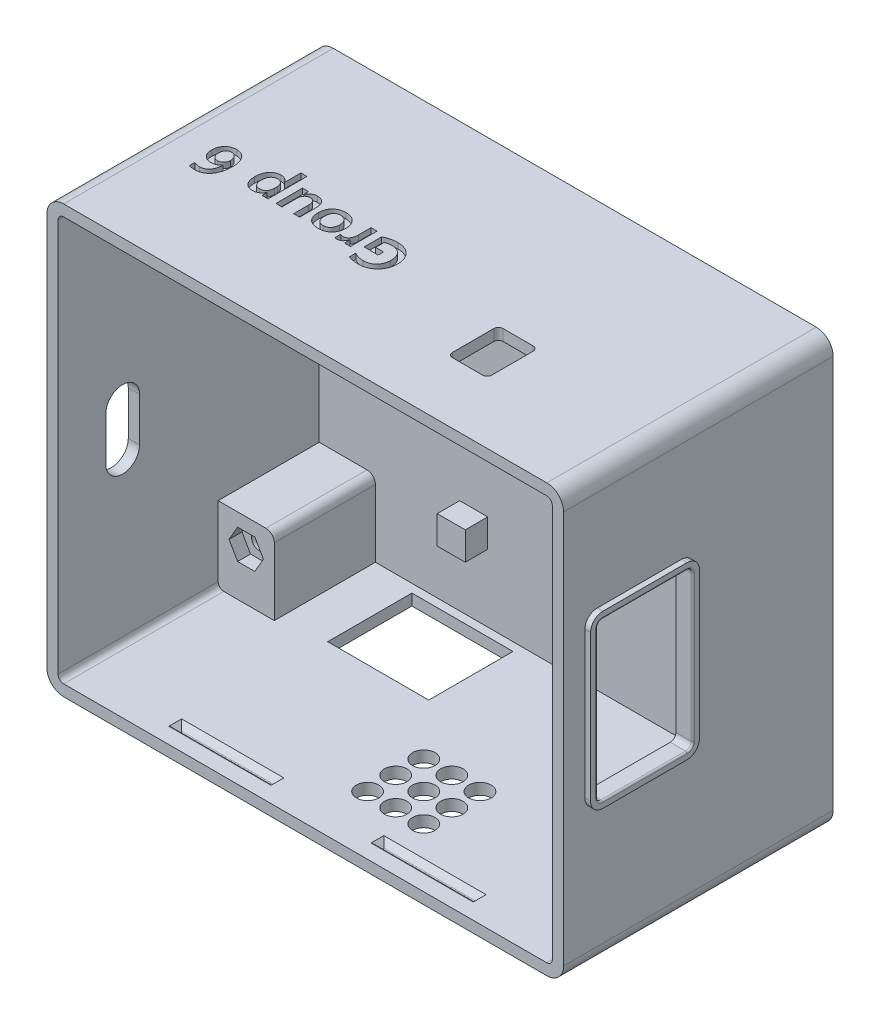
SolidWorks part; units mm, degrees
ref_plane "前视基准面" through (0, 0, 0) normal (0, 0, 1) x (1, 0, 0)
ref_plane "上视基准面" through (0, 0, 0) normal (0, 1, 0) x (1, 0, 0)
ref_plane "右视基准面" through (0, 0, 0) normal (1, 0, 0) x (0, 0, -1)
other "Configuration Table"
sketch "草图1" plane through (0, 0, 0) normal (0, 0, 1) x (1, 0, 0)
  line L5 (3, 0) -> (89, 0)
  line L6 (0, 3) -> (0, 73)
  line L7 (3, 76) -> (89, 76)
  line L8 (92, 3) -> (92, 73)
  arc A0 (89, 76) -> (92, 73) centre (89, 73) cw
  arc A1 (89, 0) -> (92, 3) centre (89, 3) ccw
  arc A2 (3, 0) -> (0, 3) centre (3, 3) cw
  arc A3 (0, 73) -> (3, 76) centre (3, 73) cw
  point P7 (92, 76)
  point P10 (92, 0)
  point P13 (0, 0)
  point P16 (0, 76)
  dimension "D3" = 3
  dimension "D1" = 92
  dimension "D2" = 76
extrude "凸台-拉伸1" add sketch "草图1" along normal blind 1.5 contours L5 A1 L8 A0 L7 A3 L6 A2
sketch "草图3" plane through (0, 0, 0) normal (0, 0, 1) x (1, 0, 0)
  line L1 (3, 0) -> (89, 0) construction
  line L2 (92, 3) -> (92, 73) construction
  line L3 (3, 76) -> (89, 76) construction
  line L4 (0, 3) -> (0, 73) construction
  line L5 (3, 0) -> (89, 0)
  line L6 (92, 3) -> (92, 73)
  line L7 (3, 76) -> (89, 76)
  line L8 (0, 3) -> (0, 73)
  line L9 (2, 3) -> (2, 73)
  line L10 (3, 74) -> (89, 74)
  line L11 (90, 3) -> (90, 73)
  line L12 (3, 2) -> (89, 2)
  arc A0 (0, 3) -> (3, 0) centre (3, 3) ccw construction
  arc A1 (89, 0) -> (92, 3) centre (89, 3) ccw construction
  arc A2 (92, 73) -> (89, 76) centre (89, 73) ccw construction
  arc A3 (3, 76) -> (0, 73) centre (3, 73) ccw construction
  arc A4 (0, 3) -> (3, 0) centre (3, 3) ccw
  arc A5 (89, 0) -> (92, 3) centre (89, 3) ccw
  arc A6 (92, 73) -> (89, 76) centre (89, 73) ccw
  arc A7 (3, 76) -> (0, 73) centre (3, 73) ccw
  arc A8 (3, 74) -> (2, 73) centre (3, 73) ccw
  arc A9 (90, 73) -> (89, 74) centre (89, 73) ccw
  arc A10 (89, 2) -> (90, 3) centre (89, 3) ccw
  arc A11 (2, 3) -> (3, 2) centre (3, 3) ccw
  dimension "D1" = 2
extrude "凸台-拉伸2" add sketch "草图3" along normal blind 48
sketch "草图4" plane through (0, 0, 0) normal (0, 0, 1) x (1, 0, 0)
  line L0 (1.5, 39.5) -> (104.4077, 39.5) construction
  line L1 (88.06, 68.5) -> (86.53, 65.85)
  line L2 (46, 69.5) -> (46, 1.5) construction
  line L3 (86.53, 71.15) -> (88.06, 68.5)
  line L4 (81.94, 68.5) -> (83.47, 71.15)
  line L5 (2, 73) -> (2, 3) construction
  line L6 (83.47, 71.15) -> (86.53, 71.15)
  line L7 (12, 5) -> (12, 2)
  line L8 (12, 74) -> (12, 65)
  line L9 (89, 74) -> (3, 74) construction
  line L10 (10.5, 63.5) -> (2, 63.5)
  line L11 (2, 73) -> (2, 3) construction
  line L12 (83.47, 65.85) -> (81.94, 68.5)
  line L13 (8.53, 65.85) -> (10.06, 68.5)
  line L14 (10.06, 68.5) -> (8.53, 71.15)
  line L15 (8.53, 71.15) -> (5.47, 71.15)
  line L16 (5.47, 71.15) -> (3.94, 68.5)
  line L17 (3.94, 68.5) -> (5.47, 65.85)
  line L18 (5.47, 65.85) -> (8.53, 65.85)
  line L19 (86.53, 65.85) -> (83.47, 65.85)
  line L20 (81.5, 63.5) -> (90, 63.5)
  line L21 (80, 74) -> (80, 65)
  line L22 (81.94, 10.5) -> (83.47, 7.85)
  line L23 (83.47, 7.85) -> (86.53, 7.85)
  line L24 (86.53, 7.85) -> (88.06, 10.5)
  line L25 (88.06, 10.5) -> (86.53, 13.15)
  line L26 (86.53, 13.15) -> (83.47, 13.15)
  line L27 (83.47, 13.15) -> (81.94, 10.5)
  line L28 (80, 5) -> (80, 14)
  line L29 (81.5, 15.5) -> (90, 15.5)
  line L30 (8.53, 13.15) -> (10.06, 10.5)
  line L31 (3.94, 10.5) -> (5.47, 13.15)
  line L32 (5.47, 13.15) -> (8.53, 13.15)
  line L33 (5.47, 7.85) -> (3.94, 10.5)
  line L34 (10.06, 10.5) -> (8.53, 7.85)
  line L35 (8.53, 7.85) -> (5.47, 7.85)
  line L36 (12, 5) -> (12, 14)
  line L37 (10.5, 15.5) -> (2, 15.5)
  line L38 (80, 5) -> (80, 2)
  line L40 (90, 3) -> (90, 73) construction
  line L41 (3, 2) -> (89, 2) construction
  line L42 (3, 2) -> (89, 2) construction
  line L43 (90, 3) -> (90, 73)
  line L44 (3, 2) -> (89, 2)
  line L45 (2, 73) -> (2, 3)
  line L46 (89, 74) -> (3, 74)
  circle A1 centre (7, 68.5) radius 1.35
  circle A2 centre (85, 68.5) radius 2.65 construction
  arc A3 (12, 65) -> (10.5, 63.5) centre (10.5, 65) cw
  circle A4 centre (7, 68.5) radius 2.65 construction
  circle A5 centre (85, 68.5) radius 1.35
  arc A6 (80, 65) -> (81.5, 63.5) centre (81.5, 65) ccw
  circle A7 centre (85, 10.5) radius 2.65 construction
  circle A8 centre (85, 10.5) radius 1.35
  arc A9 (80, 14) -> (81.5, 15.5) centre (81.5, 14) cw
  arc A10 (12, 14) -> (10.5, 15.5) centre (10.5, 14) ccw
  circle A11 centre (7, 10.5) radius 2.65 construction
  circle A12 centre (7, 10.5) radius 1.35
  arc A13 (90, 73) -> (89, 74) centre (89, 73) ccw construction
  arc A14 (89, 2) -> (90, 3) centre (89, 3) ccw construction
  arc A15 (2, 3) -> (3, 2) centre (3, 3) ccw construction
  arc A16 (3, 74) -> (2, 73) centre (3, 73) ccw construction
  arc A17 (90, 73) -> (89, 74) centre (89, 73) ccw
  arc A18 (89, 2) -> (90, 3) centre (89, 3) ccw
  arc A19 (2, 3) -> (3, 2) centre (3, 3) ccw
  arc A20 (3, 74) -> (2, 73) centre (3, 73) ccw
  dimension "D3" = 1.5
  dimension "D4" = 2.7
  dimension "D2" = 10.5
  dimension "D5" = 10
  dimension "D6" = 5.5
  dimension "D7" = 5.3
  dimension "D9" = 10
  dimension "D10" = 13.5
extrude "凸台-拉伸5" add sketch "草图4" along normal blind 19.5 contours L45 A19 L44 L36 A10 L37 L34 L35 L33 L31 L32 L30 | L44 A18 L43 L29 A9 L28 L27 L26 L25 L24 L23 L22 | L43 A17 L46 L21 A6 L20 L1 L19 L12 L4 L6 L3 | L46 A20 L45 L10 A3 L8 L18 L17 L16 L15 L14 L13 region at (11.832, 3.5, 0) region at (80.168, 3.5, 0) region at (2.145, 68.25, 0) region at (85.75, 63.645, 0)
extrude "凸台-拉伸7" add sketch "草图4<9>" along normal blind 17.2 contours L19 L1 L3 L6 L4 L12 A5 | L26 L27 L22 L23 L24 L25 A8 | L35 L34 L30 L32 L31 L33 A12 | L17 L18 L13 L14 L15 L16 A1 region at (87.2249, 67.2155, 0) region at (7, 65.931, 0) region at (82.7751, 11.7845, 0) region at (9.2249, 11.7845, 0)
sketch "草图4<9>" plane through (0, 0, 0) normal (0, 0, 1) x (1, 0, 0) same geometry as "草图4"
sketch "草图10" plane through (92, 0, 0) normal (1, 0, 0) x (0, 0, -1)
  line L0 (0, 3) -> (0, 73) construction
  line L1 (-42, 54) -> (-27, 54)
  line L2 (-43, 53) -> (-43, 27)
  line L3 (-42, 26) -> (-27, 26)
  line L4 (-26, 53) -> (-26, 27)
  line L5 (2, 40.5) -> (-63.4567, 40.5) construction
  line L6 (-43, 40) -> (-26, 40) construction
  line L8 (-46, 40.5) -> (0, 40.5) construction
  line L9 (-48, 73) -> (0, 73) construction
  line L10 (-48, 3) -> (0, 3) construction
  arc A0 (-43, 27) -> (-42, 26) centre (-42, 27) ccw
  arc A1 (-27, 26) -> (-26, 27) centre (-27, 27) ccw
  arc A2 (-27, 54) -> (-26, 53) centre (-27, 53) cw
  arc A3 (-42, 54) -> (-43, 53) centre (-42, 53) ccw
  point P17 (-43, 26)
  point P21 (-26, 26)
  point P24 (-26, 54)
  dimension "D7" = 1
  dimension "D1" = 26
  dimension "D2" = 28
  dimension "D3" = 70
  dimension "D4" = 17
  dimension "D5" = 19
extrude "切除-拉伸1" cut sketch "草图10" against normal blind 2
sketch "草图11" plane through (0, 0, 0) normal (-1, 0, 0) x (0, 0, 1)
  line L1 (48, 3) -> (0, 3) construction
  line L2 (33.5, 72.2956) -> (33.5, -1.5996) construction
  line L3 (0, 3) -> (0, 73) construction
  line L4 (36.5, 38.9) -> (36.5, 31.1) construction
  line L5 (39.5, 38.9) -> (39.5, 31.1)
  line L6 (33.5, 38.9) -> (33.5, 31.1)
  line L7 (0, 35.5) -> (65.5855, 35.5) construction
  arc A0 (39.5, 38.9) -> (33.5, 38.9) centre (36.5, 38.9) ccw
  arc A1 (33.5, 31.1) -> (39.5, 31.1) centre (36.5, 31.1) ccw
  point P8 (36.5, 35)
  dimension "D1" = 33.5
  dimension "D2" = 0
  dimension "D3" = 6
  dimension "D4" = 7.8
  dimension "D5" = 32
extrude "切除-拉伸2" cut sketch "草图11" against normal blind 2
sketch "草图12" plane through (0, 74, 0) normal (0, -1, 0) x (1, 0, 0)
  line L0 (80, 1.5) -> (12, 1.5) construction
  line L12 (18, 46) -> (38, 46)
  line L13 (18, 46) -> (18, 42)
  line L14 (18, 42) -> (38, 42)
  line L15 (38, 46) -> (38, 42)
  line L16 (3, 48) -> (3, 19.5) construction
  line L17 (54, 46) -> (74, 46)
  line L18 (54, 46) -> (54, 42)
  line L19 (54, 42) -> (74, 42)
  line L20 (74, 46) -> (74, 42)
  line L21 (89, 48) -> (89, 19.5) construction
  dimension "D1" = 4
  dimension "D2" = 20
  dimension "D3" = 40.5
  dimension "D4" = 15
  dimension "D5" = 40.5
  dimension "D6" = 16
  dimension "D7" = 15
  dimension "D8" = 4
ref_plane "基准面1" through (46, 0, 0) normal (1, 0, 0) x (0, 0, -1)
ref_plane "基准面2" through (0, 38, 0) normal (0, -1, 0) x (-1, 0, 0)
sketch "草图17" plane through (0, 0, 0) normal (0, -1, 0) x (1, 0, 0)
  line L0 (3, 0) -> (89, 0) construction
  line L1 (20, 18) -> (38, 18)
  line L2 (20, 18) -> (20, 3)
  line L3 (20, 3) -> (38, 3)
  line L4 (38, 18) -> (38, 3)
  line L5 (3, 48) -> (3, 0) construction
  line L6 (29, 6.35) -> (29, 46) construction
  point P6 (20, 10.5)
  point P10 (29, 18)
  dimension "D1" = 18
  dimension "D2" = 3
  dimension "D3" = 18
  dimension "D4" = 17
extrude "切除-拉伸3" cut sketch "草图17" against normal blind 2.5
extrude "切除-拉伸4" cut sketch "草图12" against normal blind 1.1
chamfer "倒角30" distance 2 angle 45 4 edges at (28, 75.1, 46) (38, 75.1, 44) (28, 75.1, 42) (18, 75.1, 44)
chamfer "倒角31" distance 2 angle 45 4 edges at (64, 75.1, 46) (74, 75.1, 44) (64, 75.1, 42) (54, 75.1, 44)
mirror "镜向6" about plane through (0, 38, 0) normal (0, -1, 0) of "切除-拉伸4"
chamfer "倒角32" distance 2 angle 45 4 edges at (64, 0.9, 42) (74, 0.9, 44) (64, 0.9, 46) (54, 0.9, 44)
chamfer "倒角33" distance 2 angle 45 4 edges at (28, 0.9, 42) (38, 0.9, 44) (28, 0.9, 46) (18, 0.9, 44)
fillet "圆角32" radius 0.2 1 edges at (28, 0.9, 44)
fillet "圆角33" radius 0.2 1 edges at (64, 0.9, 44)
fillet "圆角34" radius 0.2 1 edges at (64, 75.1, 44)
fillet "圆角35" radius 0.2 1 edges at (28, 75.1, 44)
sketch "草图18" plane through (0, 0, 0) normal (0, -1, 0) x (1, 0, 0)
  line L0 (89, 48) -> (89, 0) construction
  line L1 (46.55, 37) -> (56.55, 37)
  line L2 (46.55, 37) -> (46.55, 27)
  line L3 (46.55, 27) -> (56.55, 27)
  line L4 (56.55, 37) -> (56.55, 27)
  line L5 (3, 0) -> (89, 0) construction
  line L7 (46.55, 26.9807) -> (46.55, 26.062)
  line L8 (46.65, 27.541) -> (51.65, 27.541) construction
  circle A0 centre (46.65, 37.541) radius 2
  circle A1 centre (51.65, 37.541) radius 2
  circle A2 centre (56.65, 37.541) radius 2
  circle A3 centre (46.65, 32.541) radius 2
  circle A4 centre (51.65, 32.541) radius 2
  circle A5 centre (56.65, 32.541) radius 2
  circle A6 centre (46.65, 27.541) radius 2
  circle A7 centre (51.65, 27.541) radius 2
  circle A8 centre (56.65, 27.541) radius 2
  point P13 (51.55, 37)
  dimension "D5" = 3
  dimension "D6" = 5
  dimension "D8" = 5
  dimension "D1" = 32.45
  dimension "D2" = 10
  dimension "D3" = 10
  dimension "D4" = 27
  dimension "D10" = 5
  dimension "D7" = 3
  dimension "D9" = 3
extrude "切除-拉伸6" cut sketch "草图18" against normal blind 3 contours L1 A0 L2 | L2 A0 L1 | L1 A1 | L1 A1 | L1 A2 L4 | L4 A2 L1 | L4 A5 | L4 A5 | L2 A3 | A4 | L2 A3 | A6 L3 L2 | L3 A6 L2 | L3 A8 L4 | L4 A8 L3 | L3 A7 | L3 A7 region at (46.495, 0, 37.7889) region at (47.3728, 0, 36.3851) region at (51.65, 0, 38.1062) region at (51.65, 0, 36.3932) region at (47.4451, 0, 32.541) region at (45.7469, 0, 32.541) region at (56.8007, 0, 37.7473) region at (55.8178, 0, 36.4024) region at (47.481, 0, 28.1155) region at (46.1921, 0, 27.2245) region at (57.4451, 0, 32.541) region at (55.7469, 0, 32.541) region at (51.65, 0, 28.1062) region at (51.65, 0, 26.3932) region at (57.0808, 0, 27.2862) region at (55.7123, 0, 28.0956) region at (51.65, 0, 32.541)
sketch "草图21" plane through (0, 76, 0) normal (0, 1, 0) x (1, 0, 0)
  line L0 (89, -48) -> (89, 0) construction
  line L1 (61.3, -28.1) -> (66.7, -28.1)
  line L2 (60.5, -28.9) -> (60.5, -36.3)
  line L3 (61.3, -37.1) -> (66.7, -37.1)
  line L4 (67.5, -28.9) -> (67.5, -36.3)
  line L5 (60.5, -28.1) -> (67.5, -37.1) construction
  line L6 (60.5, -37.1) -> (67.5, -28.1) construction
  line L7 (89, -48) -> (3, -48) construction
  arc A0 (66.7, -37.1) -> (67.5, -36.3) centre (66.7, -36.3) ccw
  arc A1 (60.5, -36.3) -> (61.3, -37.1) centre (61.3, -36.3) ccw
  arc A2 (66.7, -28.1) -> (67.5, -28.9) centre (66.7, -28.9) cw
  arc A3 (61.3, -28.1) -> (60.5, -28.9) centre (61.3, -28.9) ccw
  point P0 (64, -32.6)
  dimension "D5" = 0.8
  dimension "D1" = 25
  dimension "D2" = 15.4
  dimension "D3" = 9
  dimension "D4" = 7
extrude "切除-拉伸7" cut sketch "草图21" against normal blind 5
sketch "草图27" plane through (92, 0, 0) normal (1, 0, 0) x (0, 0, -1)
  line L20 (-27, 54) -> (-42, 54) construction
  line L21 (-26, 27) -> (-26, 53) construction
  line L22 (-43, 53) -> (-43, 27) construction
  line L23 (-42, 26) -> (-27, 26) construction
  line L24 (-42, 24.8) -> (-27, 24.8)
  line L25 (-44.2, 53) -> (-44.2, 27)
  line L26 (-24.8, 27) -> (-24.8, 53)
  line L27 (-27, 55.2) -> (-42, 55.2)
  line L28 (-42, 24.8) -> (-27, 24.8)
  line L29 (-44.2, 53) -> (-44.2, 27)
  line L30 (-24.8, 27) -> (-24.8, 53)
  line L31 (-27, 55.2) -> (-42, 55.2)
  line L32 (-27, 54) -> (-42, 54)
  line L33 (-26, 27) -> (-26, 53)
  line L34 (-43, 53) -> (-43, 27)
  line L35 (-42, 26) -> (-27, 26)
  arc A4 (-26, 53) -> (-27, 54) centre (-27, 53) ccw construction
  arc A5 (-42, 54) -> (-43, 53) centre (-42, 53) ccw construction
  arc A6 (-27, 26) -> (-26, 27) centre (-27, 27) ccw construction
  arc A7 (-43, 27) -> (-42, 26) centre (-42, 27) ccw construction
  arc A8 (-44.2, 27) -> (-42, 24.8) centre (-42, 27) ccw
  arc A9 (-27, 24.8) -> (-24.8, 27) centre (-27, 27) ccw
  arc A10 (-42, 55.2) -> (-44.2, 53) centre (-42, 53) ccw
  arc A11 (-24.8, 53) -> (-27, 55.2) centre (-27, 53) ccw
  arc A12 (-44.2, 27) -> (-42, 24.8) centre (-42, 27) ccw
  arc A13 (-27, 24.8) -> (-24.8, 27) centre (-27, 27) ccw
  arc A14 (-42, 55.2) -> (-44.2, 53) centre (-42, 53) ccw
  arc A15 (-24.8, 53) -> (-27, 55.2) centre (-27, 53) ccw
  arc A16 (-26, 53) -> (-27, 54) centre (-27, 53) ccw
  arc A17 (-42, 54) -> (-43, 53) centre (-42, 53) ccw
  arc A18 (-27, 26) -> (-26, 27) centre (-27, 27) ccw
  arc A19 (-43, 27) -> (-42, 26) centre (-42, 27) ccw
  dimension "D1" = 1.2
extrude "凸台-拉伸8" add sketch "草图27" along normal blind 1
fillet "圆角36" radius 0.3 8 edges at (93, 26.2929, 26.2929) (93, 26, 34.5) (93, 26.2929, 42.7071) (93, 40, 43) (93, 53.7071, 42.7071) (93, 54, 34.5) (93, 53.7071, 26.2929) (93, 40, 26)
sketch "草图30" plane through (0, 76, 0) normal (0, 1, 0) x (1, 0, 0)
  line L0 (7.5, -24.2894) -> (45.1631, -24.2894) construction
  text T0 "Group 6" font "@Yu Gothic UI" height in points 26
extrude "切除-拉伸14" cut sketch "草图30" against normal blind 1
sketch "草图31" plane through (0, 0, 1.5) normal (0, 0, 1) x (1, 0, 0)
  line L0 (12, 2) -> (80, 2) construction
  line L1 (27, 19) -> (32, 19)
  line L2 (27, 19) -> (27, 14)
  line L3 (27, 14) -> (32, 14)
  line L4 (32, 19) -> (32, 14)
  line L5 (27, 19) -> (32, 14) construction
  line L6 (27, 14) -> (32, 19) construction
  line L7 (90, 15.5) -> (90, 63.5) construction
  point P0 (29.5, 16.5)
  dimension "D1" = 5
  dimension "D2" = 5
  dimension "D3" = 12
  dimension "D4" = 58
extrude "凸台-拉伸9" add sketch "草图31" along normal blind 4
fillet "圆角37" radius 0.3 1 edges at (28, 74, 45.1)
fillet "圆角38" radius 0.3 1 edges at (64, 74, 45.1)
fillet "圆角39" radius 0.3 1 edges at (64, 2, 45.1)
fillet "圆角40" radius 0.3 1 edges at (28, 2, 45.1)
